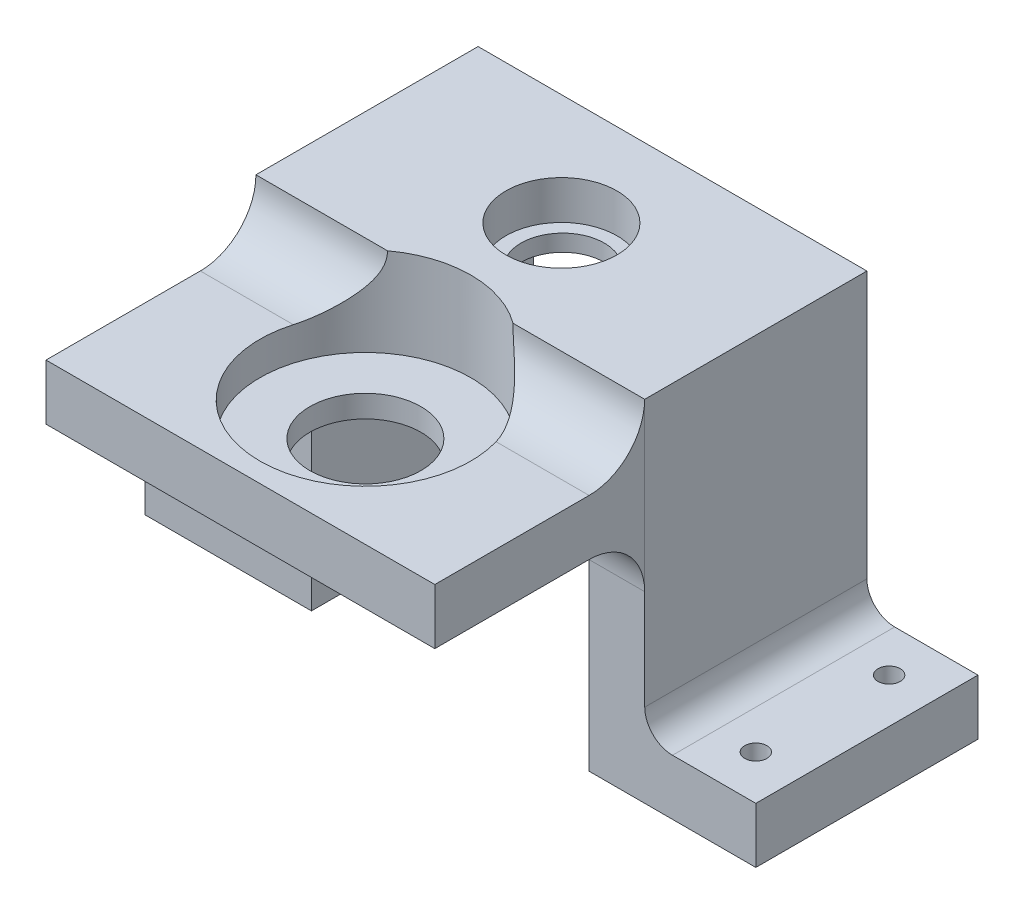
SolidWorks part; units mm, degrees
material "ABS"
ref_plane "Front Plane" through (0, 0, 0) normal (0, 0, 1) x (1, 0, 0)
ref_plane "Top Plane" through (0, 0, 0) normal (0, 1, 0) x (1, 0, 0)
ref_plane "Right Plane" through (0, 0, 0) normal (1, 0, 0) x (0, 0, -1)
sketch "Sketch1" plane through (0, 0, 0) normal (0, 1, 0) x (1, 0, 0)
  line L0 (0, 20) -> (0, -20) construction
  line L1 (-35, -20) -> (35, -20)
  line L2 (-35, -20) -> (-35, 20)
  line L3 (-35, 20) -> (35, 20)
  line L4 (35, -20) -> (35, 20)
  line L5 (-35, -20) -> (35, 20) construction
  line L6 (-35, 20) -> (35, -20) construction
  circle A5 centre (0, 0.2229) radius 7.5
  point P0 (0, 0)
  dimension "D3" = 15
  dimension "D1" = 70
  dimension "D2" = 40
extrude "Boss-Extrude2" add sketch "Sketch1" along normal blind 10
sketch "Sketch2" plane through (0, 10, 0) normal (0, 1, 0) x (1, 0, 0)
  circle A0 centre (0, 0) radius 10
  dimension "D1" = 20
extrude "Cut-Extrude1" cut sketch "Sketch2" against normal blind 7
sketch "Sketch3" plane through (0, 0, 0) normal (0, -1, 0) x (1, 0, 0)
  line L0 (-35, 20) -> (35, 20) construction
  line L1 (-35, -20) -> (-25, -20)
  line L2 (-35, -20) -> (-35, 20)
  line L3 (-35, 20) -> (-25, 20)
  line L4 (-25, -20) -> (-25, 20)
  dimension "D1" = 10
extrude "Boss-Extrude3" add sketch "Sketch3" along normal blind 53
sketch "Sketch5" plane through (0, -53, 0) normal (0, -1, 0) x (1, 0, 0)
  line L1 (-25, -20) -> (-55, -20)
  line L2 (-25, -20) -> (-25, 20)
  line L3 (-25, 20) -> (-55, 20)
  line L4 (-55, -20) -> (-55, 20)
  dimension "D1" = 40
  dimension "D2" = 30
extrude "Boss-Extrude4" add sketch "Sketch5" against normal blind 10
sketch "Sketch7" plane through (0, -53, 0) normal (0, -1, 0) x (1, 0, 0)
  line L0 (-25, 20) -> (-55, 20) construction
  line L1 (-55, 20) -> (-55, -20) construction
  line L2 (-55, -20) -> (-25, -20) construction
  circle A0 centre (-47, 12) radius 2
  circle A1 centre (-47, -12) radius 2
  dimension "D1" = 4
  dimension "D2" = 4
  dimension "D3" = 8
  dimension "D4" = 8
  dimension "D5" = 8
  dimension "D6" = 8
extrude "Cut-Extrude2" cut sketch "Sketch7" against normal blind 10
fillet "Fillet5" radius 5 1 edges at (-35, -43, 0)
mirror "Mirror10" about plane through (0, 0, 0) normal (1, 0, 0) of "Boss-Extrude3", "Boss-Extrude4", "Cut-Extrude2"
fillet "Fillet6" radius 5 1 edges at (35, -43, 0)
sketch "Sketch8" plane through (0, 0, 20) normal (0, 0, 1) x (1, 0, 0)
  line L0 (35, 10) -> (35, -38) construction
  line L1 (-35, 10) -> (35, 10)
  line L2 (-35, 10) -> (-35, 0)
  line L3 (-35, 0) -> (35, 0)
  line L4 (35, 10) -> (35, 0)
sketch "Sketch10" plane through (0, 0, 0) normal (0, 1, 0) x (1, 0, 0)
  line L1 (-35.0136, -57.7771) -> (34.9864, -57.7771)
  line L2 (-35.0136, -57.7771) -> (-35.0136, -12.7771)
  line L3 (-35.0136, -12.7771) -> (34.9864, -12.7771)
  line L4 (34.9864, -57.7771) -> (34.9864, -12.7771)
  line L5 (-35.0136, -57.7771) -> (34.9864, -12.7771) construction
  line L6 (-35.0136, -12.7771) -> (34.9864, -57.7771) construction
  circle A0 centre (-0.0136, -35.2771) radius 10
  circle A1 centre (0, 0.2229) radius 7.5 construction
  point P0 (-0.0136, -35.2771)
  dimension "D3" = 20
  dimension "D4" = 35.5
  dimension "D1" = 70
  dimension "D2" = 45
extrude "Boss-Extrude9" add sketch "Sketch10" against normal blind 10
sketch "Sketch11" plane through (0, 0, 0) normal (0, 1, 0) x (1, 0, 0)
  circle A0 centre (-0.0136, -35.2771) radius 19
  dimension "D1" = 38
extrude "Cut-Extrude3" cut sketch "Sketch11" against normal blind 6 and the other way through all
fillet "Fillet7" radius 10 3 edges at (29.9932, -10, 20) (23.1346, 0, 20) (-23.155, 0, 20)
fillet "Fillet8" radius 10 4 edges at (25, 0, -3.6114) (-25, 0, -3.6114) (-25, -10, 21.3886) (25, -10, 21.3886)
fillet "Fillet9" radius 5 5 edges at (-25, -15, 12.7771) (-22.0711, -2.9289, 12.7771) (0, 0, 12.7771) (22.0711, -2.9289, 12.7771) (25, -15, 12.7771)
